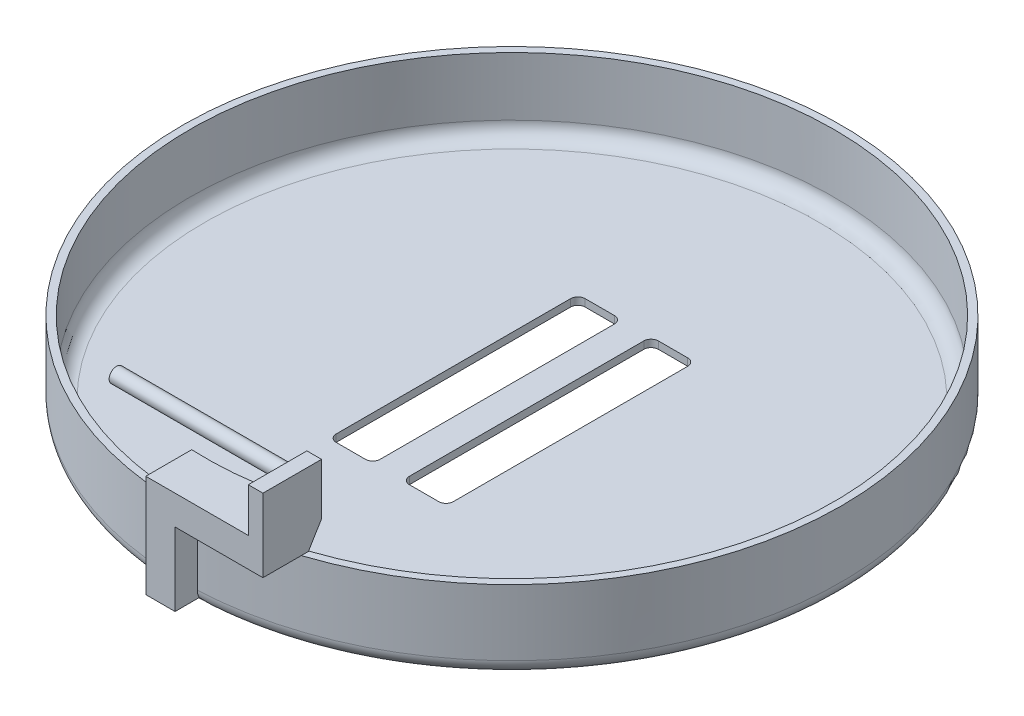
SolidWorks part; units mm, degrees
ref_plane "Front Plane" through (0, 0, 0) normal (0, 0, 1) x (1, 0, 0)
ref_plane "Top Plane" through (0, 0, 0) normal (0, 1, 0) x (1, 0, 0)
ref_plane "Right Plane" through (0, 0, 0) normal (1, 0, 0) x (0, 0, -1)
sketch "Sketch1" plane through (0, 0, 0) normal (0, 1, 0) x (1, 0, 0)
  circle A0 centre (0, 0) radius 22
  circle A1 centre (0, 0) radius 22.5
  dimension "D1" = 44
  dimension "D2" = 45
extrude "Boss-Extrude1" add sketch "Sketch1" along normal blind 5
sketch "Sketch3" plane through (0, 0, 0) normal (0, 1, 0) x (1, 0, 0)
  circle A0 centre (0, 0) radius 22.5
extrude "Boss-Extrude2" add sketch "Sketch3" against normal blind 0.5
sketch "Sketch5" plane through (0, 0, 0) normal (0, 1, 0) x (1, 0, 0)
  circle A0 centre (0, 0) radius 10
sketch "Sketch6" plane through (0, -0.5, 0) normal (0, -1, 0) x (1, 0, 0)
  line L1 (4, -8.5) -> (1, -8.5)
  line L2 (4, -8.5) -> (4, 8.5)
  line L3 (-1, 8.5) -> (-4, 8.5)
  line L4 (4, 8.5) -> (1, 8.5)
  line L5 (1, -8.5) -> (1, 8.5)
  line L6 (-1, 8.5) -> (-1, -8.5)
  line L7 (-1, -8.5) -> (-4, -8.5)
  line L8 (-4, 8.5) -> (-4, -8.5)
  line L9 (-1, 8.5) -> (-4, -8.5) construction
  line L10 (-1, -8.5) -> (-4, 8.5) construction
  line L11 (4, -8.5) -> (1, 8.5) construction
  line L12 (4, 8.5) -> (1, -8.5) construction
  circle A0 centre (0, 0) radius 22.5 construction
  point P0 (0, 0)
  point P1 (-2.5, 0)
  point P9 (2.5, 0)
  dimension "D1" = 2.5
  dimension "D2" = 2.5
extrude "Cut-Extrude1" cut sketch "Sketch6" against normal blind 10 and the other way blind 10
fillet "Fillet1" radius 0.5 8 edges at (1, -0.25, 8.5) (-4, -0.25, 8.5) (-1, -0.25, 8.5) (4, -0.25, 8.5) (-1, -0.25, -8.5) (-4, -0.25, -8.5) (1, -0.25, -8.5) (4, -0.25, -8.5)
fillet "Fillet3" radius 1 2 edges at (0, -0.5, 22.5) (0, 0, 22)
sketch "Sketch7" plane through (0, 5, 0) normal (0, 1, 0) x (1, 0, 0)
  line L1 (1, -20) -> (-1, -20)
  line L2 (1, -20) -> (1, -24)
  line L3 (1, -24) -> (-1, -24)
  line L4 (-1, -20) -> (-1, -24)
  line L5 (1, -20) -> (-1, -24) construction
  line L6 (1, -24) -> (-1, -20) construction
  circle A0 centre (0, 0) radius 22 construction
  circle A1 centre (0, 0) radius 22 construction
  point P0 (0, -22)
extrude "Boss-Extrude3" add sketch "Sketch7" against normal blind 5 and the other way blind 2
sketch "Sketch8" plane through (1, 0, 0) normal (1, 0, 0) x (0, 0, -1)
  line L0 (-20, 7) -> (-20, 0) construction
  line L1 (-24, 7) -> (-20, 7)
  line L2 (-24, 7) -> (-24, 5)
  line L3 (-24, 5) -> (-20, 5)
  line L4 (-20, 7) -> (-20, 5)
extrude "Boss-Extrude4" add sketch "Sketch8" along normal blind 6
sketch "Sketch9" plane through (0, 7, 0) normal (0, 1, 0) x (1, 0, 0)
  line L1 (-1, -24) -> (7, -24) construction
  line L2 (7, -20) -> (6, -20)
  line L3 (7, -20) -> (7, -24)
  line L4 (7, -24) -> (6, -24)
  line L5 (6, -20) -> (6, -24)
extrude "Boss-Extrude5" add sketch "Sketch9" along normal blind 3
sketch "Sketch10" plane through (6, 0, 0) normal (-1, 0, 0) x (0, 0, 1)
  line L0 (20, 10) -> (24, 10) construction
  line L1 (24, 10) -> (24, 7) construction
  circle A0 centre (21, 9) radius 0.5
  dimension "D1" = 1
  dimension "D2" = 3
extrude "Boss-Extrude6" add sketch "Sketch10" along normal blind 12
sketch "Sketch12" plane through (0, 0, 0) normal (1, 0, 0) x (0, 0, -1)
  line L0 (-18, 12) -> (-22, 5.0718)
  line L1 (0, 0) -> (-21, 0)
  line L2 (0, 0) -> (0, 12)
  line L3 (0, 12) -> (-18, 12)
  line L4 (-22, 1) -> (-22, 5.0718)
  arc A0 (-21, 0) -> (-22, 1) centre (-21, 1) cw
  point P2 (-22, 12)
  dimension "D1" = 1
  dimension "D2" = 4
  dimension "D3" = 60
ref_axis "Axis1" through (0, 12.625, 0) along (0, -1, 0)
revolve "Cut-Revolve1" cut sketch "Sketch12" angle 360 about axis through (0, 12.625, 0) along (0, -1, 0)
